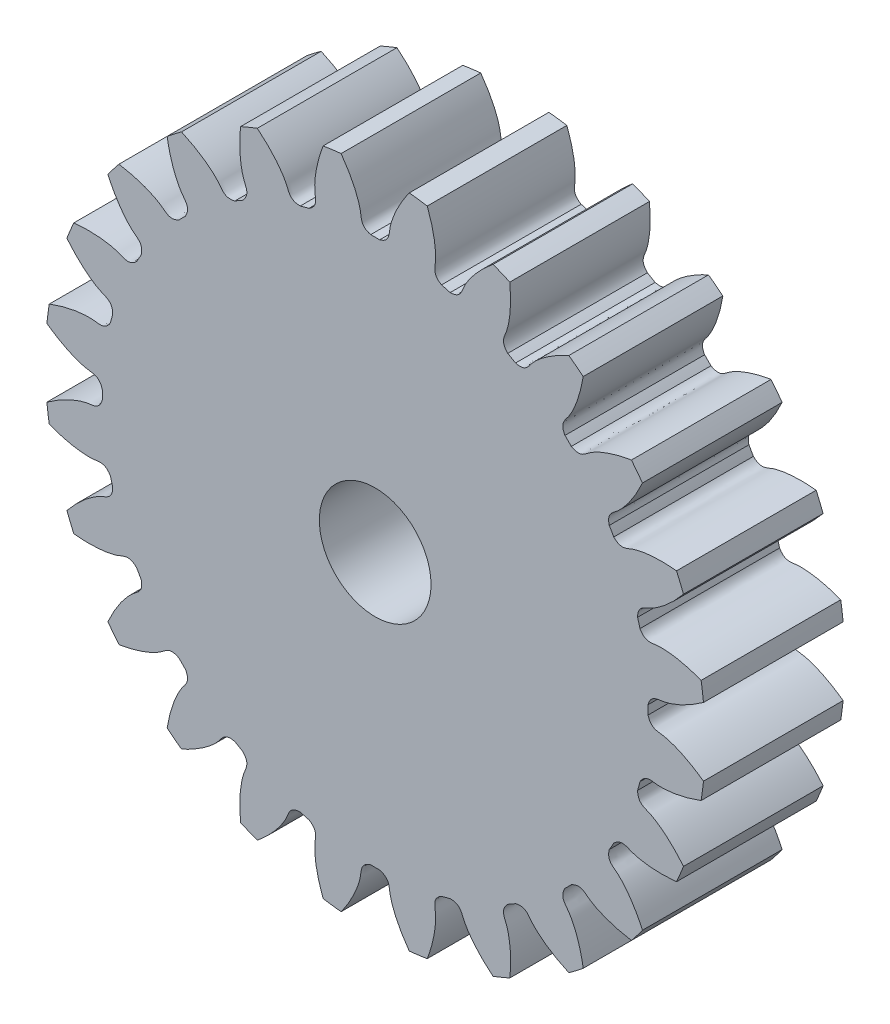
SolidWorks part; units mm, degrees
ref_plane "前视基准面" through (0, 0, 0) normal (0, 0, 1) x (1, 0, 0)
ref_plane "上视基准面" through (0, 0, 0) normal (0, 1, 0) x (1, 0, 0)
ref_plane "右视基准面" through (0, 0, 0) normal (1, 0, 0) x (0, 0, -1)
sketch "草图1" plane through (0, 0, 0) normal (0, 0, 1) x (1, 0, 0)
  circle A0 centre (0, 0) radius 6.5
extrude "凸台-拉伸1" add sketch "草图1" along normal blind 2.75
ref_axis "基准轴1" through (0, 0, 2.75) along (0, 0, -1)
sketch "草图2" plane through (0, 0, 0) normal (0, 0, 1) x (1, 0, 0)
  line L0 (0, 0) -> (0, 6.5) construction
  circle A0 centre (0, 0) radius 6.5 construction
  arc A1 (0.0884, 5.3743) -> (-0.0884, 5.3743) centre (0, 0) ccw
  arc A2 (1.5578, 7.3471) -> (-1.5578, 7.3471) centre (0, 0) ccw
  spline S0 degree 3 poles (0.0884, 5.3743) (0.284, 5.4284) (0.2695, 5.5579) (0.2931, 5.6863) (0.2965, 5.7029) (0.3007, 5.7216) (0.3058, 5.7424) (0.312, 5.7653) (0.3191, 5.7902) (0.3275, 5.8171) (0.3371, 5.846) (0.348, 5.8769) (0.3604, 5.9096) (0.3742, 5.9441) (0.3896, 5.9805) (0.4067, 6.0185) (0.4254, 6.0583) (0.446, 6.0997) (0.4684, 6.1427) (0.4928, 6.1872) (0.5192, 6.2332) (0.5476, 6.2806) (0.5782, 6.3293) (0.611, 6.3792) (0.6461, 6.4304) (0.6834, 6.4827) (0.7232, 6.536) (0.7654, 6.5903) (0.8101, 6.6456) (0.8574, 6.7016) (0.9073, 6.7583) (0.9598, 6.8158) (1.015, 6.8738) (1.0729, 6.9322) (1.1336, 6.9911) (1.1972, 7.0503) (1.2635, 7.1097) (1.3328, 7.1693) (1.4302, 7.2497) (1.506, 7.3084) (1.5578, 7.3471) knots 0 0 0 0 0.143961 0.149818 0.156577 0.164236 0.172796 0.182258 0.19262 0.203884 0.216049 0.229115 0.243082 0.25795 0.273719 0.290389 0.30796 0.326433 0.345806 0.366081 0.387257 0.409333 0.432311 0.45619 0.48097 0.506651 0.533234 0.560717 0.589101 0.618387 0.648574 0.679661 0.71165 0.74454 0.778331 0.813023 0.848616 0.885111 0.922506 1 1 1 1
  spline S1 degree 3 poles (-0.0884, 5.3743) (-0.284, 5.4284) (-0.2695, 5.5579) (-0.2931, 5.6863) (-0.2965, 5.7029) (-0.3007, 5.7216) (-0.3058, 5.7424) (-0.312, 5.7653) (-0.3191, 5.7902) (-0.3275, 5.8171) (-0.3371, 5.846) (-0.348, 5.8769) (-0.3604, 5.9096) (-0.3742, 5.9441) (-0.3896, 5.9805) (-0.4067, 6.0185) (-0.4254, 6.0583) (-0.446, 6.0997) (-0.4684, 6.1427) (-0.4928, 6.1872) (-0.5192, 6.2332) (-0.5476, 6.2806) (-0.5782, 6.3293) (-0.611, 6.3792) (-0.6461, 6.4304) (-0.6834, 6.4827) (-0.7232, 6.536) (-0.7654, 6.5903) (-0.8101, 6.6456) (-0.8574, 6.7016) (-0.9073, 6.7583) (-0.9598, 6.8158) (-1.015, 6.8738) (-1.0729, 6.9322) (-1.1336, 6.9911) (-1.1972, 7.0503) (-1.2635, 7.1097) (-1.3328, 7.1693) (-1.4302, 7.2497) (-1.506, 7.3084) (-1.5578, 7.3471) knots 0 0 0 0 0.143961 0.149818 0.156577 0.164236 0.172796 0.182258 0.19262 0.203884 0.216049 0.229115 0.243082 0.25795 0.273719 0.290389 0.30796 0.326433 0.345806 0.366081 0.387257 0.409333 0.432311 0.45619 0.48097 0.506651 0.533234 0.560717 0.589101 0.618387 0.648574 0.679661 0.71165 0.74454 0.778331 0.813023 0.848616 0.885111 0.922506 1 1 1 1
extrude "切除-拉伸1" cut sketch "草图2" along normal through all
pattern_circular "阵列(圆周)1" count 24 every 15 about axis through (0, 0, 2.75) along (0, 0, -1) of "切除-拉伸1"
sketch "草图3" plane through (0, 0, 0) normal (0, 0, 1) x (1, 0, 0)
  circle A0 centre (0, 0) radius 6 construction
  dimension "Dn" = 12
sketch "草图4" plane through (0, 0, 2.75) normal (0, 0, 1) x (1, 0, 0)
  circle A0 centre (0, 0) radius 1.1
  dimension "D1" = 2.2
extrude "切除-拉伸2" cut sketch "草图4" against normal up to next
